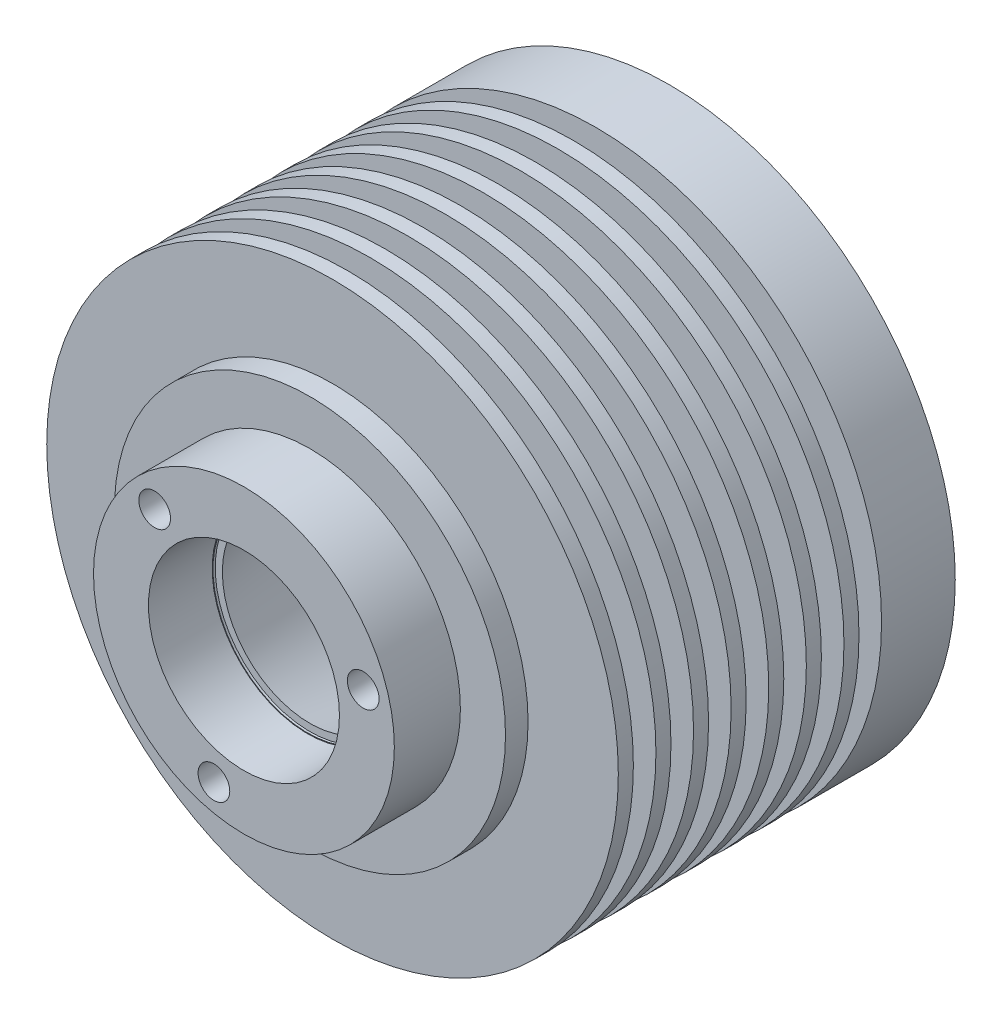
SolidWorks part; units mm, degrees
ref_plane "Plan de face" through (0, 0, 0) normal (0, 0, 1) x (1, 0, 0)
ref_plane "Plan de dessus" through (0, 0, 0) normal (0, 1, 0) x (1, 0, 0)
ref_plane "Plan de droite" through (0, 0, 0) normal (1, 0, 0) x (0, 0, -1)
sketch "Esquisse1" plane through (0, 0, 0) normal (0, 0, 1) x (1, 0, 0)
  circle A0 centre (0, 0) radius 12.7
  circle A1 centre (0, 0) radius 20
extrude "Boss.-Extru.1" add sketch "Esquisse1" along normal blind 8.78
sketch "Esquisse2" plane through (0, 0, 0) normal (0, 0, -1) x (-1, 0, 0)
  circle A0 centre (0, 0) radius 11.2
  circle A1 centre (0, 0) radius 38
extrude "Boss.-Extru.2" add sketch "Esquisse2" along normal blind 47.8
chamfer "Chanfrein3" distance 49.8 angle 12.675 1 edges at (-11.2, 0, -47.8)
sketch "Esquisse3" [suppressed] plane through (0, 0, 7.7) normal (0, 0, 1) x (1, 0, 0)
  line L0 (-12.7, 0) -> (-17.7, 0)
  line L1 (12.7, 0) -> (17.7, 0)
  circle A0 centre (0, 0) radius 12.7 construction
  circle A1 centre (0, 0) radius 17.7 construction
  circle A2 centre (0, 0) radius 12.7 construction
other "PerçageAvancé1" [suppressed] parameters "D0"=0
sketch "Esquisse4" plane through (0, 0, 7.7) normal (0, 0, 1) x (1, 0, 0)
  line L0 (-12.7, 0) -> (-17.7, 0) construction
  line L1 (12.7, 0) -> (17.7, 0) construction
  point P0 (-15.2, 0)
  point P4 (15.2, 0)
sketch "Esquisse5" plane through (-15.2, 0, 7.7) normal (0, 1, 0) x (1, 0, 0)
  line L0 (0, 0) -> (0, 1.1176)
  line L1 (0, -0.5588) -> (0, 1.6764) construction
  line L2 (1.7856, 0) -> (1.7856, 1.1176)
  line L3 (0, 0) -> (1.7856, 0)
  line L4 (1.7856, 1.1176) -> (0, 1.1176)
  dimension "D1" = 1.1176
  dimension "D2" = 3.5712
sketch "Sketch1" plane through (0, 0, 8.78) normal (0, 0, 1) x (1, 0, 0)
  line L0 (-12.7, 0) -> (-20, 0)
  line L1 (-20, 0) -> (12.7, 0)
  line L2 (12.7, 0) -> (20, 0)
  circle A0 centre (0, 0) radius 12.7 construction
  circle A1 centre (0, 0) radius 12.7 construction
  circle A2 centre (0, 0) radius 20 construction
sketch "Sketch7" plane through (0, 0, 0) normal (0, 0, 1) x (1, 0, 0)
  circle A0 centre (0, 0) radius 26
  circle A1 centre (0, 0) radius 38
extrude "Cut-Extrude2" cut sketch "Sketch7" against normal blind 3
sketch "Sketch12" plane through (0, 0, -47.8) normal (0, 0, -1) x (-1, 0, 0)
  line L0 (38, 0) -> (34, 0)
  circle A0 centre (0, 0) radius 38 construction
sketch "Sketch16" plane through (0, 0, -47.8) normal (0, 0, -1) x (-1, 0, 0)
  line L0 (-28.8376, 24.7466) -> (-28.8376, 8.27)
  circle A0 centre (0, 0) radius 38 construction
hole_wizard "Hole for #4 300® SC Nuts (SP)2" positions "Sketch17" profile "Sketch19" hole size "#4-40" standard "PEM® Inch"
sketch "Sketch17" plane through (0, 0, -47.8) normal (0, 0, -1) x (-1, 0, 0)
  point P0 (-28.8376, 8.27)
sketch "Sketch19" plane through (28.8376, 8.27, -47.8) normal (1, 0, 0) x (0, 1, 0)
  line L0 (0, 0) -> (0, 6.2667)
  line L1 (0, 6.2667) -> (2.1082, 5)
  line L2 (2.1082, 5) -> (2.1082, 0)
  line L5 (2.1082, 0) -> (0, 0)
  line L10 (0, 6.2667) -> (-2.1082, 5) construction
  line L11 (0, -6.35) -> (0, 107.95) construction
  dimension "Hole Dia." = 4.2164
  dimension "Hole Depth" = 5
  dimension "Drill Angle" = 118
pattern_circular "CirPattern1" count 3 over 360 about axis through (0, 0, 0) along (0, 0, 1) of "Hole for #4 300® SC Nuts (SP)2"
sketch "Sketch20" plane through (0, 0, 8.78) normal (0, 0, 1) x (1, 0, 0)
  line L0 (15.8607, 12.1836) -> (15.8607, 4.5485)
  circle A0 centre (0, 0) radius 20 construction
hole_wizard "Hole for #4 300® SC Nuts (SP)3" positions "Sketch21" profile "Sketch22" hole size "#4-40" standard "PEM® Inch"
sketch "Sketch21" plane through (0, 0, 8.78) normal (0, 0, 1) x (1, 0, 0)
  point P0 (15.8607, 4.5485)
sketch "Sketch22" plane through (15.8607, 4.5485, 8.78) normal (1, 0, 0) x (0, -1, 0)
  line L0 (0, 0) -> (0, 6.2667)
  line L1 (0, 6.2667) -> (2.1082, 5)
  line L2 (2.1082, 5) -> (2.1082, 0)
  line L5 (2.1082, 0) -> (0, 0)
  line L10 (0, 6.2667) -> (-2.1082, 5) construction
  line L11 (0, -6.35) -> (0, 107.95) construction
  dimension "Hole Dia." = 4.2164
  dimension "Hole Depth" = 5
  dimension "Drill Angle" = 118
pattern_circular "CirPattern2" count 3 over 360 about axis through (0, 0, 0) along (0, 0, 1) of "Hole for #4 300® SC Nuts (SP)3"
sketch "Sketch23" plane through (0, 0, 0) normal (0, 0, 1) x (1, 0, 0)
  circle A0 centre (0, 0) radius 12.6
  circle A1 centre (0, 0) radius 13.7
extrude "Boss-Extrude1" add sketch "Sketch23" along normal blind 0.3
pattern_linear "LPattern1" count 8 spacing 5 along (0, 0, -1) of "Cut-Extrude2"
